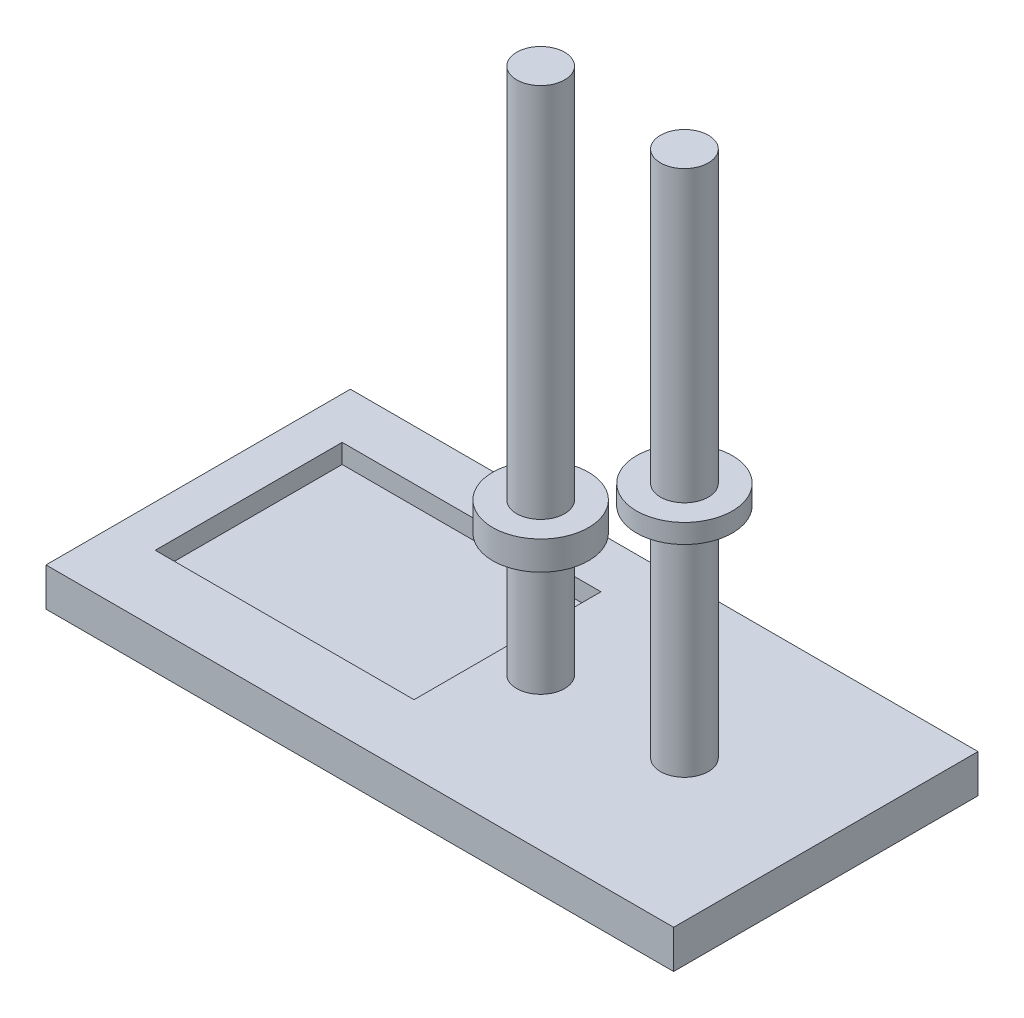
SolidWorks part; units mm, degrees
note: The reader was unsure of these and kept them because the rebuilt part matched: shared geometry of "Sketch1<3>".
ref_plane "Front Plane" through (0, 0, 0) normal (0, 0, 1) x (1, 0, 0)
ref_plane "Top Plane" through (0, 0, 0) normal (0, 1, 0) x (1, 0, 0)
ref_plane "Right Plane" through (0, 0, 0) normal (1, 0, 0) x (0, 0, -1)
sketch "Sketch1" plane through (0, 0, 0) normal (0, 1, 0) x (1, 0, 0)
  line L0 (-7.3925, 10.6445) -> (-7.3925, -8.8555)
  line L1 (-43.7678, -20.877) -> (43.7678, -20.877)
  line L2 (-43.7678, -20.877) -> (-43.7678, 20.877)
  line L3 (-43.7678, 20.877) -> (43.7678, 20.877)
  line L4 (43.7678, -20.877) -> (43.7678, 20.877)
  line L5 (-43.7678, -20.877) -> (43.7678, 20.877) construction
  line L6 (-43.7678, 20.877) -> (43.7678, -20.877) construction
  line L8 (-34.3925, -8.8555) -> (-7.3925, -8.8555)
  line L9 (-34.3925, -8.8555) -> (-34.3925, 10.6445)
  line L10 (-34.3925, 10.6445) -> (-7.3925, 10.6445)
  line L11 (-7.3925, -8.8555) -> (-7.3925, 10.6445)
  circle A0 centre (-18.039, 0) radius 5
  circle A1 centre (-3.039, 0) radius 10
  circle A2 centre (-3.039, 0) radius 5
  circle A3 centre (11.961, 0) radius 10
  circle A4 centre (11.961, 0) radius 5
  circle A5 centre (11.961, 0) radius 2.5
  circle A7 centre (-3.039, 0) radius 2.5
  point P0 (0, 0)
  dimension "D1" = 10
  dimension "D2" = 20
  dimension "D5" = 5
  dimension "D3" = 19.5
  dimension "D4" = 27
sketch "Sketch2" plane through (0, 0, 0) normal (0, 1, 0) x (1, 0, 0)
  line L2 (-43.7678, -20.877) -> (43.7678, -20.877)
  line L3 (-43.7678, -20.877) -> (-43.7678, 20.877)
  line L4 (-43.7678, 20.877) -> (43.7678, 20.877)
  line L5 (43.7678, -20.877) -> (43.7678, 20.877)
  line L6 (-43.7678, -20.877) -> (43.7678, 20.877) construction
  line L7 (-43.7678, 20.877) -> (43.7678, -20.877) construction
  point P2 (0, 0)
extrude "Boss-Extrude1" add sketch "Sketch2" against normal blind 4
extrude "Boss-Extrude2" add sketch "Sketch1" along normal blind 55 contours A5 | A7
ref_plane "Plane1" through (0, 24.8, 0) normal (0, 1, 0) x (1, 0, 0)
sketch "Sketch4" plane through (0, 24.8, 0) normal (0, 1, 0) x (1, 0, 0)
  circle A0 centre (11.961, 0) radius 5
  dimension "D1" = 10
extrude "Boss-Extrude3" add sketch "Sketch4" against normal blind 2
sketch "Sketch5" plane through (0, 0, 0) normal (0, 1, 0) x (1, 0, 0)
  line L1 (-43.7678, 20.877) -> (43.7678, 20.877)
  line L2 (-43.7678, 20.877) -> (-43.7678, -20.877)
  line L3 (-43.7678, -20.877) -> (43.7678, -20.877)
  line L4 (43.7678, 20.877) -> (43.7678, -20.877)
  line L8 (-38.7678, -15.877) -> (26.7095, -15.877)
  line L9 (-38.7678, 15.877) -> (-38.7678, -15.877)
  line L10 (-38.7678, 15.877) -> (26.7095, 15.877)
  line L11 (26.7095, 15.877) -> (26.7095, -15.877)
  line L12 (-38.7678, 15.877) -> (43.7678, 15.877) construction
  line L13 (-38.7678, -15.877) -> (43.7678, -15.877) construction
  dimension "D1" = 5
extrude "Cut-Extrude5" cut sketch "Sketch5" against normal blind 10
ref_plane "Plane2" through (0, 15.8, 0) normal (0, 1, 0) x (1, 0, 0)
sketch "Sketch6" plane through (0, 15.8, 0) normal (0, 1, 0) x (1, 0, 0)
  circle A0 centre (-3.039, 0) radius 5
  dimension "D1" = 10
extrude "Boss-Extrude4" add sketch "Sketch6" against normal blind 3
extrude "Cut-Extrude1" cut sketch "Sketch1<3>" against normal blind 2 contours A1 L11 L10 L9 L8 A0 | L11 A1 | L0 A2
sketch "Sketch1<3>" plane through (0, 0, 0) normal (0, 1, 0) x (1, 0, 0) same geometry as "Sketch1"
equation "\"smalldia\"=10"
equation "\"D1@Sketch1\"=\"smalldia\""
equation "\"largedia\"=20"
equation "\"D2@Sketch1\"=\"largedia\""
